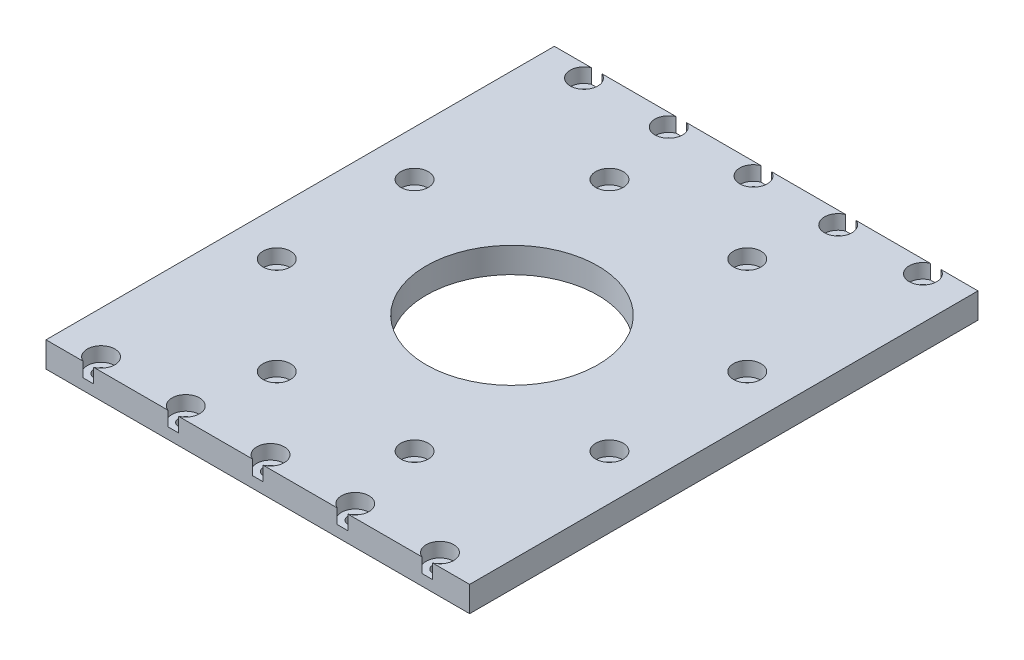
SolidWorks part; units mm, degrees
material "6061-T6 (SS)"
ref_plane "Front Plane" through (0, 0, 0) normal (0, 0, 1) x (1, 0, 0)
ref_plane "Top Plane" through (0, 0, 0) normal (0, 1, 0) x (1, 0, 0)
ref_plane "Right Plane" through (0, 0, 0) normal (1, 0, 0) x (0, 0, -1)
sketch "Sketch1" plane through (0, 0, 0) normal (0, 1, 0) x (1, 0, 0)
  circle A0 centre (0, 0) radius 50
  circle A1 centre (0, 0) radius 20.25
  dimension "D1" = 100
  dimension "D2" = 40.5
extrude "Boss-Extrude1" add sketch "Sketch1" along normal blind 6
sketch "Sketch2" plane through (0, 6, 0) normal (0, 1, 0) x (1, 0, 0)
  line L0 (-16.264, 39.2649) -> (16.264, 39.2649) construction
  circle A0 centre (0, 0) radius 42.5 construction
  point P4 (-16.264, 39.2649)
  point P10 (16.264, 39.2649)
  point P11 (39.2649, 16.264)
  point P12 (39.2649, -16.264)
  point P13 (16.264, -39.2649)
  point P14 (-16.264, -39.2649)
  point P15 (-39.2649, -16.264)
  point P16 (-39.2649, 16.264)
  dimension "D1" = 85
  dimension "D2" = 8
hole_wizard "CBORE for M3 Hex Socket Head Cap Screw2" positions "Sketch2" profile "Sketch3" counterbore size "M3" standard "DIN" end condition through all
sketch "Sketch3" plane through (-39.2649, 6, -16.264) normal (1, 0, 0) x (0, 0, 1)
  line L0 (0, 0) -> (0, 6)
  line L1 (0, 6) -> (1.7, 6)
  line L3 (1.7, 6) -> (1.7, 3.4)
  line L4 (1.7, 3.4) -> (3.25, 3.4)
  line L5 (3.25, 3.4) -> (3.25, 0)
  line L7 (3.25, 0) -> (0, 0)
  line L11 (0, -6.35) -> (0, 107.95) construction
  dimension "Thru Hole Dia." = 3.4
  dimension "Thru Hole Depth" = 6
  dimension "C'Bore Dia." = 6.5
  dimension "C'Bore Depth" = 3.4
sketch "Sketch6" plane through (0, 6, 0) normal (0, 1, 0) x (1, 0, 0)
  line L0 (-50, 0) -> (-50, -60)
  line L1 (-50, -60) -> (50, -60)
  line L2 (50, -60) -> (50, 0)
  circle A0 centre (0, 0) radius 50 construction
  arc A1 (-50, 0) -> (50, 0) centre (0, 0) ccw
  dimension "D1" = 60
extrude "Boss-Extrude2" add sketch "Sketch6" against normal up to surface (6 mm away) up to face at (-16.264, 0, -37.5649)
sketch "Sketch10" plane through (0, 6, 0) normal (0, 1, 0) x (1, 0, 0)
  line L0 (-50, 0) -> (-50, 60)
  line L1 (-50, 60) -> (50, 60)
  line L2 (50, 60) -> (50, 0)
  arc A0 (50, 0) -> (-50, 0) centre (0, 0) ccw construction
  arc A1 (50, 0) -> (-50, 0) centre (0, 0) ccw
  dimension "D1" = 60
extrude "Boss-Extrude3" add sketch "Sketch10" against normal up to surface (6 mm away) up to face at (-16.264, 0, -37.5649)
sketch "Sketch11" plane through (0, 6, 0) normal (0, 1, 0) x (1, 0, 0)
  line L0 (50, 60) -> (-50, 60) construction
  line L3 (0, 0) -> (0, 57) construction
  line L4 (0, 0) -> (-50000, 0) construction
  point P0 (-40, 57)
  point P13 (-20, 57)
  point P14 (0, 57)
  point P15 (20, 57)
  point P16 (40, 57)
  point P57 (40, -57)
  point P58 (20, -57)
  point P59 (0, -57)
  point P60 (-20, -57)
  point P61 (-40, -57)
  dimension "D1" = 3
  dimension "D2" = 5
  dimension "D5" = 20
hole_wizard "CBORE for M3 Hex Socket Head Cap Screw1" positions "Sketch11" profile "Sketch12" counterbore size "M3" standard "DIN" end condition through all
sketch "Sketch12" plane through (-40, 6, -57) normal (1, 0, 0) x (0, 0, 1)
  line L0 (0, 0) -> (0, 6)
  line L1 (0, 6) -> (1.7, 6)
  line L3 (1.7, 6) -> (1.7, 3.4)
  line L4 (1.7, 3.4) -> (3.25, 3.4)
  line L5 (3.25, 3.4) -> (3.25, 0)
  line L7 (3.25, 0) -> (0, 0)
  line L11 (0, -6.35) -> (0, 107.95) construction
  dimension "Thru Hole Dia." = 3.4
  dimension "Thru Hole Depth" = 6
  dimension "C'Bore Dia." = 6.5
  dimension "C'Bore Depth" = 3.4
